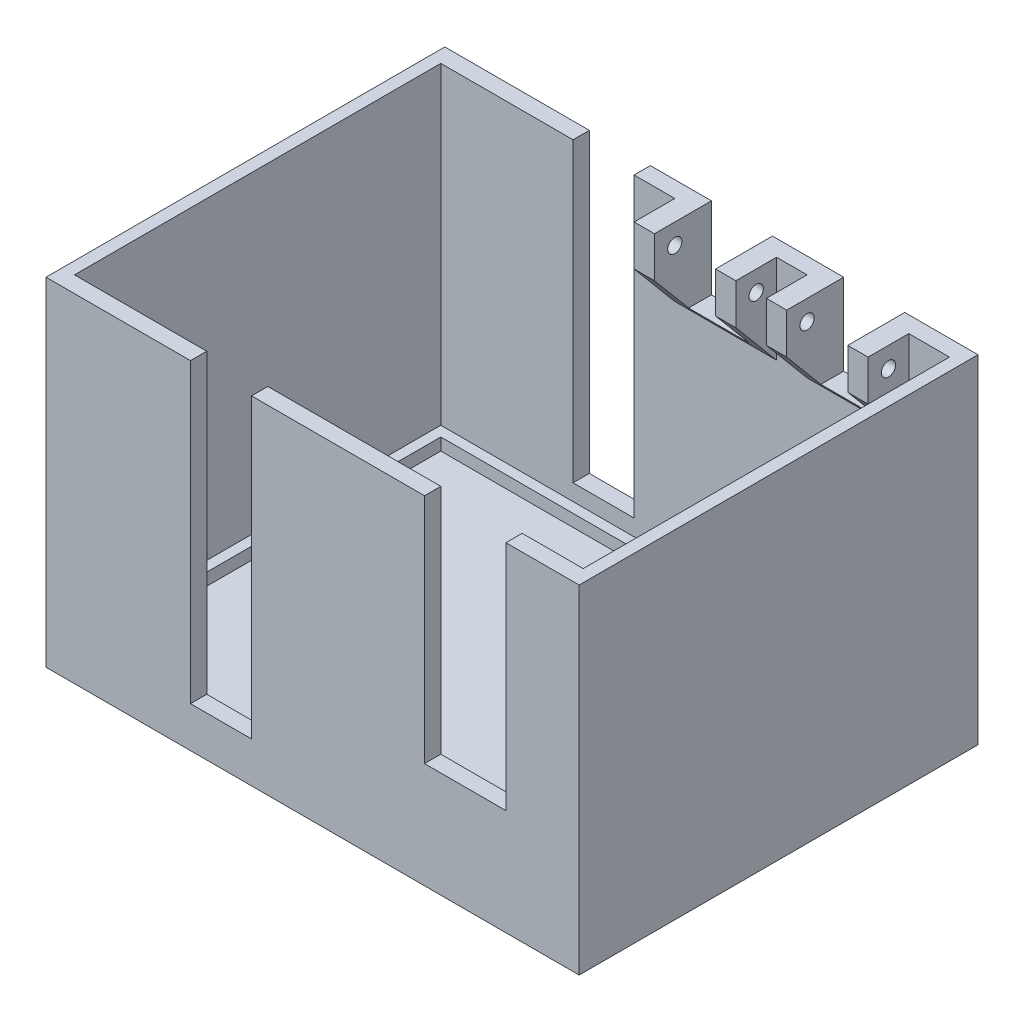
SolidWorks part; units mm, degrees
ref_plane "Front Plane" through (0, 0, 0) normal (0, 0, 1) x (1, 0, 0)
ref_plane "Top Plane" through (0, 0, 0) normal (0, 1, 0) x (1, 0, 0)
ref_plane "Right Plane" through (0, 0, 0) normal (1, 0, 0) x (0, 0, -1)
sketch "Sketch1" plane through (0, 0, 0) normal (0, 1, 0) x (1, 0, 0)
  line L1 (62.5, -45) -> (-62.5, -45)
  line L2 (62.5, -45) -> (62.5, 45)
  line L3 (62.5, 45) -> (-62.5, 45)
  line L4 (-62.5, -45) -> (-62.5, 45)
  line L5 (62.5, -45) -> (-62.5, 45) construction
  line L6 (62.5, 45) -> (-62.5, -45) construction
  line L7 (65.5, -49) -> (-65.5, -49)
  line L8 (65.5, -49) -> (65.5, 49)
  line L9 (65.5, 49) -> (-65.5, 49)
  line L10 (-65.5, -49) -> (-65.5, 49)
  line L11 (65.5, -49) -> (-65.5, 49) construction
  line L12 (65.5, 49) -> (-65.5, -49) construction
  point P0 (0, 0)
  point P5 (0, 0)
  dimension "D4" = 4
  dimension "D1" = 125
  dimension "D2" = 90
  dimension "D3" = 3
extrude "Boss-Extrude1" add sketch "Sketch1" along normal blind 80
sketch "Sketch2" plane through (0, 0, 0) normal (0, -1, 0) x (1, 0, 0)
  line L1 (65.5, -49) -> (-65.5, -49)
  line L2 (65.5, -49) -> (65.5, 49)
  line L3 (65.5, 49) -> (-65.5, 49)
  line L4 (-65.5, -49) -> (-65.5, 49)
extrude "Boss-Extrude2" add sketch "Sketch2" along normal blind 3
sketch "Sketch4" plane through (0, 0, 0) normal (0, 1, 0) x (1, 0, 0)
  line L1 (-62.5, 45) -> (62.5, 45)
  line L2 (-62.5, 45) -> (-62.5, -45)
  line L3 (-62.5, -45) -> (62.5, -45)
  line L4 (62.5, 45) -> (62.5, -45)
  line L5 (59.5, -42) -> (-60, -42)
  line L6 (59.5, -42) -> (59.5, 42.5)
  line L7 (59.5, 42.5) -> (-60, 42.5)
  line L8 (-60, -42) -> (-60, 42.5)
  dimension "D1" = 2.5
  dimension "D2" = 2.5
  dimension "D3" = 3
  dimension "D4" = 3
extrude "Boss-Extrude3" add sketch "Sketch4" along normal blind 3
sketch "Sketch5" plane through (0, 0, -49) normal (0, 0, -1) x (-1, 0, 0)
  line L0 (-65.5, 80) -> (65.5, 80) construction
  line L1 (15, 80) -> (30, 80)
  line L2 (15, 80) -> (15, 7)
  line L3 (15, 7) -> (30, 7)
  line L4 (30, 80) -> (30, 7)
  line L5 (15, 80) -> (30, 7) construction
  line L6 (15, 7) -> (30, 80) construction
  line L7 (62.5, 74.3372) -> (62.5, 12.8298) construction
  line L8 (65.5, 80) -> (65.5, -3) construction
  line L9 (65.5, -3) -> (-65.5, -3) construction
  point P0 (22.5, 43.5)
  dimension "D1" = 3
  dimension "D2" = 40
  dimension "D3" = 15
  dimension "D4" = 10
extrude "Cut-Extrude1" cut sketch "Sketch5" against normal through all
sketch "Sketch6" plane through (0, 0, 45) normal (0, 0, -1) x (-1, 0, 0)
  line L0 (15, 80) -> (-62.5, 80) construction
  line L1 (-27.5, 23) -> (-47.5, 23)
  line L2 (-27.5, 23) -> (-27.5, 80)
  line L3 (-27.5, 80) -> (-47.5, 80)
  line L4 (-47.5, 23) -> (-47.5, 80)
  line L5 (-27.5, 23) -> (-47.5, 80) construction
  line L6 (-27.5, 80) -> (-47.5, 23) construction
  line L7 (62.5, 3) -> (-62.5, 3) construction
  line L8 (-62.5, 80) -> (-62.5, 3) construction
  point P0 (-37.5, 51.5)
  dimension "D1" = 20
  dimension "D2" = 20
  dimension "D3" = 25
extrude "Cut-Extrude2" cut sketch "Sketch6" against normal up to next
sketch "Sketch7" plane through (0, 0, -45) normal (0, 0, 1) x (1, 0, 0)
  line L0 (62.5, 80) -> (-15, 80) construction
  line L1 (32.5, 80) -> (47.5, 80)
  line L2 (32.5, 80) -> (32.5, 60)
  line L3 (32.5, 60) -> (47.5, 60)
  line L4 (47.5, 80) -> (47.5, 60)
  line L6 (0, 80) -> (15, 80)
  line L7 (0, 80) -> (0, 60)
  line L8 (0, 60) -> (15, 60)
  line L9 (15, 80) -> (15, 60)
  dimension "D1" = 20
  dimension "D2" = 15
  dimension "D3" = 15
  dimension "D4" = 15
extrude "Cut-Extrude3" cut sketch "Sketch7" against normal up to next
sketch "Sketch8" plane through (0, 0, -45) normal (0, 0, 1) x (1, 0, 0)
  line L1 (0, 80) -> (-5, 80)
  line L2 (0, 80) -> (0, 70)
  line L3 (0, 70) -> (-5, 70)
  line L4 (-5, 80) -> (-5, 70)
  line L5 (15, 80) -> (20, 80)
  line L6 (15, 80) -> (15, 70)
  line L7 (15, 70) -> (20, 70)
  line L8 (20, 80) -> (20, 70)
  line L9 (32.5, 80) -> (27.5, 80)
  line L10 (32.5, 80) -> (32.5, 70)
  line L11 (32.5, 70) -> (27.5, 70)
  line L12 (27.5, 80) -> (27.5, 70)
  line L13 (47.5, 80) -> (52.5, 80)
  line L14 (47.5, 80) -> (47.5, 70)
  line L15 (47.5, 70) -> (52.5, 70)
  line L16 (52.5, 80) -> (52.5, 70)
  dimension "D1" = 5
  dimension "D2" = 5
  dimension "D3" = 10
  dimension "D4" = 5
  dimension "D5" = 5
extrude "Boss-Extrude4" add sketch "Sketch8" along normal blind 10
sketch "Skizze2" plane through (-5, 0, 0) normal (-1, 0, 0) x (0, 0, 1)
  line L0 (-35, 70) -> (-45, 70)
  line L1 (-45, 70) -> (-45, 58.0825)
  line L2 (-45, 58.0825) -> (-35, 70)
  dimension "D1" = 40
extrude "3D Printer Support" add sketch "Skizze2" against normal up to vertex (57.5 mm away) up to point (52.5, 70, -35)
sketch "Skizze3" plane through (0, 0, -45) normal (0, 0, -1) x (-1, 0, 0)
  line L1 (-32.5, 70) -> (-47.5, 70)
  line L2 (-32.5, 70) -> (-32.5, 60)
  line L3 (-32.5, 60) -> (-47.5, 60)
  line L4 (-47.5, 70) -> (-47.5, 60)
  line L5 (-15, 60) -> (0, 60)
  line L6 (-15, 60) -> (-15, 70)
  line L7 (-15, 70) -> (0, 70)
  line L8 (0, 60) -> (0, 70)
extrude "Schnitt-Linear austragen1" cut sketch "Skizze3" against normal blind 20
sketch "Skizze4" plane through (0, 70, 0) normal (0, 1, 0) x (1, 0, 0)
  line L1 (27.5, 45) -> (20, 45)
  line L2 (27.5, 45) -> (27.5, 35)
  line L3 (27.5, 35) -> (20, 35)
  line L4 (20, 45) -> (20, 35)
extrude "Schnitt-Linear austragen2" cut sketch "Skizze4" against normal blind 20
sketch "Skizze5" plane through (-5, 0, 0) normal (-1, 0, 0) x (0, 0, 1)
  line L0 (-35, 80) -> (-35, 70) construction
  line L1 (-35, 80) -> (-45, 80) construction
  circle A0 centre (-40, 75) radius 1.75
  point P2 (-35, 75)
  point P5 (-40, 80)
  dimension "D3" = 3.5
  dimension "D1" = 5
  dimension "D2" = 5
extrude "Schnitt-Linear austragen3" cut sketch "Skizze5" against normal up to surface (57.5 mm away) up to face at (52.5, 72.0206, -40)
